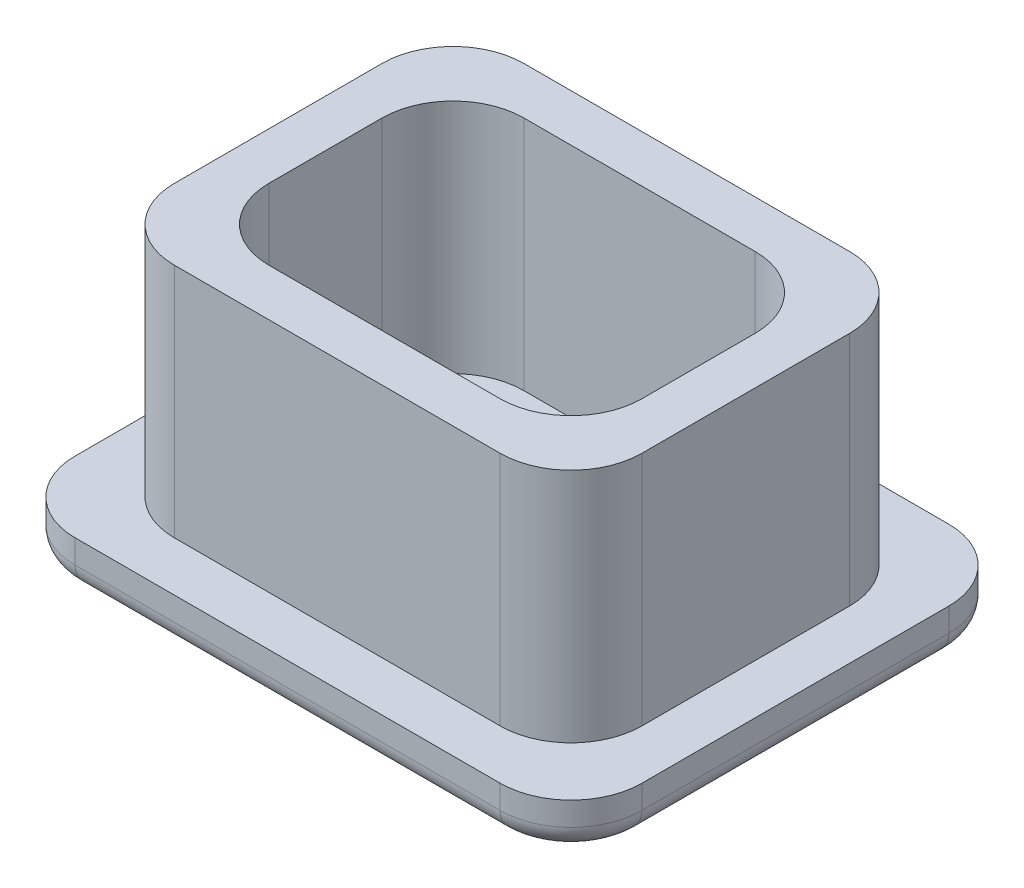
SolidWorks part; units mm, degrees
ref_plane "Front Plane" through (0, 0, 0) normal (0, 0, 1) x (1, 0, 0)
ref_plane "Top Plane" through (0, 0, 0) normal (0, 1, 0) x (1, 0, 0)
ref_plane "Right Plane" through (0, 0, 0) normal (1, 0, 0) x (0, 0, -1)
sketch "Sketch1" plane through (0, 0, 0) normal (0, 1, 0) x (1, 0, 0)
  line L1 (-38.7477, 15.4606) -> (-14.7477, 15.4606)
  line L2 (-38.7477, 15.4606) -> (-38.7477, -3.5394)
  line L3 (-38.7477, -3.5394) -> (-14.7477, -3.5394)
  line L4 (-14.7477, 15.4606) -> (-14.7477, -3.5394)
  dimension "D1" = 24
  dimension "D2" = 19
extrude "Boss-Extrude1" add sketch "Sketch1" along normal blind 2
fillet "Fillet1" radius 3 4 edges at (-38.7477, 1, -15.4606) (-38.7477, 1, 3.5394) (-14.7477, 1, -15.4606) (-14.7477, 1, 3.5394)
fillet "Fillet2" radius 1 8 edges at (-37.869, 0, 2.6607) (-38.7477, 0, -5.9606) (-37.869, 0, -14.5819) (-26.7477, 0, -15.4606) (-15.6264, 0, -14.5819) (-14.7477, 0, -5.9606) (-15.6264, 0, 2.6607) (-26.7477, 0, 3.5394)
sketch "Sketch2" plane through (0, 2, 0) normal (0, 1, 0) x (1, 0, 0)
  line L0 (-17.7477, 15.4606) -> (-35.7477, 15.4606) construction
  line L1 (-36.6477, 13.3606) -> (-16.8477, 13.3606)
  line L2 (-36.6477, 13.3606) -> (-36.6477, -1.4394)
  line L3 (-36.6477, -1.4394) -> (-16.8477, -1.4394)
  line L4 (-16.8477, 13.3606) -> (-16.8477, -1.4394)
  line L5 (-38.7477, 12.4606) -> (-38.7477, -0.5394) construction
  line L6 (-34.6477, 11.3606) -> (-18.8477, 11.3606)
  line L7 (-18.8477, 11.3606) -> (-18.8477, 0.5606)
  line L8 (-34.6477, 0.5606) -> (-18.8477, 0.5606)
  line L9 (-34.6477, 11.3606) -> (-34.6477, 0.5606)
  dimension "D1" = 19.8
  dimension "D2" = 14.8
  dimension "D3" = 2.1
  dimension "D4" = 2.1
  dimension "D5" = 2
extrude "Boss-Extrude2" add sketch "Sketch2" along normal blind 10
fillet "Fillet3" radius 3 4 edges at (-36.6477, 7, -13.3606) (-36.6477, 7, 1.4394) (-16.8477, 7, -13.3606) (-16.8477, 7, 1.4394)
fillet "Fillet4" radius 3 4 edges at (-18.8477, 7, -11.3606) (-18.8477, 7, -0.5606) (-34.6477, 7, -0.5606) (-34.6477, 7, -11.3606)
